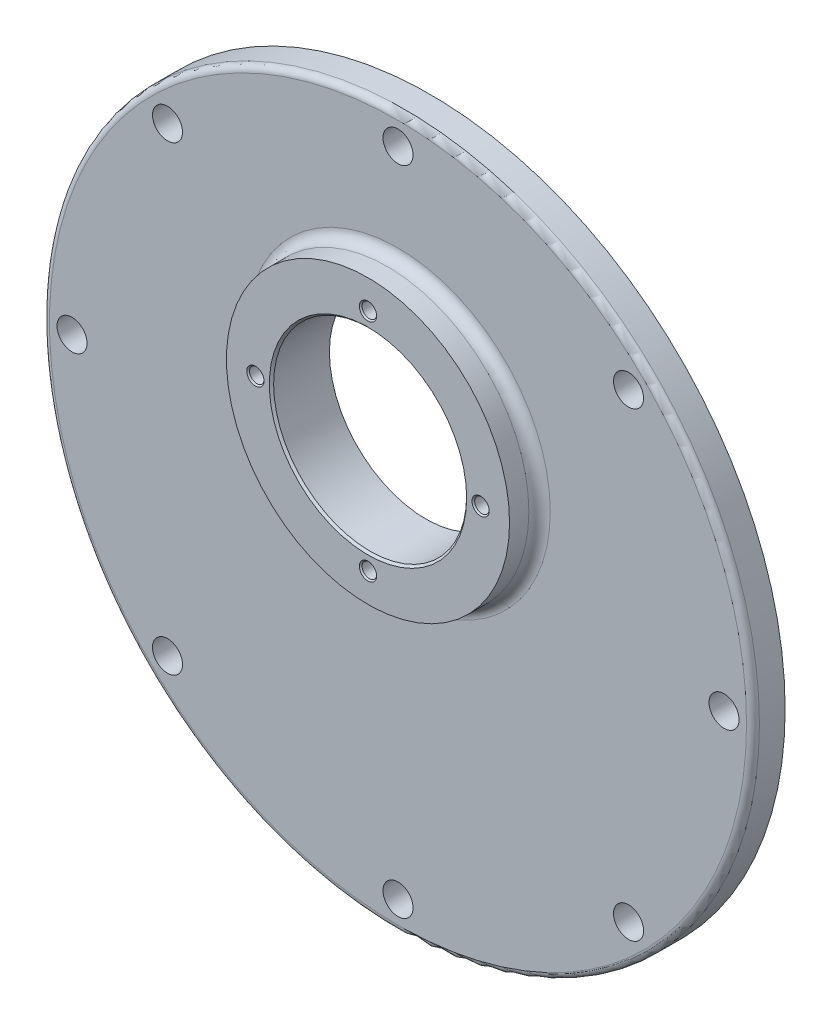
SolidWorks part; units mm, degrees
ref_plane "前视基准面" through (0, 0, 0) normal (0, 0, 1) x (1, 0, 0)
ref_plane "上视基准面" through (0, 0, 0) normal (0, 1, 0) x (1, 0, 0)
ref_plane "右视基准面" through (0, 0, 0) normal (1, 0, 0) x (0, 0, -1)
sketch "草图1" plane through (0, 0, 0) normal (0, 0, 1) x (1, 0, 0)
  circle A0 centre (0, 0) radius 140
  dimension "D1" = 280
extrude "凸台-拉伸1" add sketch "草图1" along normal blind 6
sketch "草图3" plane through (0, 0, 6) normal (0, 0, 1) x (1, 0, 0)
  circle A0 centre (0, 0) radius 165.5
  dimension "D1" = 331
extrude "凸台-拉伸2" add sketch "草图3" along normal offset from surface (15 mm away) 21 up to plane "前视基准面"
sketch "草图4" plane through (0, 0, 21) normal (0, 0, 1) x (1, 0, 0)
  line L0 (0, -11.55) -> (0, 11.55) construction
  line L1 (11.55, 0) -> (-11.55, 0) construction
  circle A0 centre (0, 40) radius 66
  dimension "D1" = 132
  dimension "D2" = 40
extrude "凸台-拉伸3" add sketch "草图4" along normal offset from surface (14 mm away) 35 up to face at (140, 0, 0)
fillet "圆角1" radius 5 1 edges at (66, 40, 21)
sketch "草图5" plane through (0, 0, 0) normal (0, 0, -1) x (-1, 0, 0)
  circle A0 centre (0, 0) radius 133
  dimension "D1" = 266
extrude "切除-拉伸1" cut sketch "草图5" against normal blind 11
sketch "草图6" plane through (0, 0, 11) normal (0, 0, -1) x (-1, 0, 0)
  circle A0 centre (0, 40) radius 55
  dimension "D1" = 110
extrude "凸台-拉伸4" add sketch "草图6" along normal blind 3
fillet "圆角2" radius 3 2 edges at (-133, 0, 11) (-55, 40, 11)
sketch "草图7" plane through (0, 0, 8) normal (0, 0, -1) x (-1, 0, 0)
  circle A0 centre (0, 40) radius 45
  dimension "D1" = 90
extrude "切除-拉伸2" cut sketch "草图7" against normal through all
chamfer "倒角1" distance 1 angle 45 1 edges at (-45, 40, 35)
sketch "草图8" plane through (0, 0, 35) normal (0, 0, 1) x (1, 0, 0)
  circle A0 centre (0, 40) radius 52.5 construction
  point P3 (52.5, 40)
  point P4 (0, 92.5)
  point P5 (-52.5, 40)
  point P6 (0, -12.5)
  dimension "D1" = 105
hole_wizard "M8 螺纹孔1" positions "草图8" profile "草图9" tap size "M8" standard "GB"
sketch "草图9" plane through (0, -12.5, 35) normal (1, 0, 0) x (0, -1, 0)
  line L0 (0, 0) -> (0, 16)
  line L1 (0, 16) -> (3.4, 13.9571)
  line L2 (3.4, 13.9571) -> (3.4, 0.625)
  line L3 (3.4, 0.625) -> (4.025, 0)
  line L5 (4.025, 0) -> (0, 0)
  line L6 (-3.4, 0.625) -> (-4.025, 0) construction
  line L10 (0, 16) -> (-3.4, 13.9571) construction
  line L11 (0, -6.35) -> (0, 107.95) construction
  dimension "螺纹孔钻头直径" = 6.8
  dimension "螺纹孔钻头深度" = 16
  dimension "近端锥形沉头孔直径" = 8.05
  dimension "近端锥形沉头孔角度" = 90
  dimension "导头角度" = 118
cosmetic thread "孔螺纹线1" parameters "D1"=14, "D2"=8
cosmetic thread "孔螺纹线2" parameters "D1"=14, "D2"=8
cosmetic thread "孔螺纹线3" parameters "D1"=14, "D2"=8
cosmetic thread "孔螺纹线4" parameters "D1"=14, "D2"=8
fillet "圆角3" radius 3 1 edges at (165.5, 0, 21)
sketch "草图10" plane through (0, 0, 21) normal (0, 0, 1) x (1, 0, 0)
  circle A0 centre (0, 0) radius 152 construction
  point P3 (152, 0)
  point P6 (107.4802, -107.4802)
  point P7 (0, -152)
  point P8 (-107.4802, -107.4802)
  point P9 (-152, 0)
  point P10 (-107.4802, 107.4802)
  point P11 (0, 152)
  point P12 (107.4802, 107.4802)
  dimension "D1" = 304
  dimension "D2" = 8
hole_wizard "孔1" positions "草图10" profile "草图11" legacy end condition through all
sketch "草图11" plane through (107.4802, 107.4802, 21) normal (1, 0, 0) x (0, -1, 0)
  line L0 (0, 0) -> (0, 21)
  line L1 (0, 21) -> (4.4, 21)
  line L2 (4.4, 21) -> (4.4, 10)
  line L3 (4.4, 10) -> (7, 10)
  line L4 (7, 10) -> (7, 0)
  line L5 (7, 0) -> (0, 0)
  line L6 (0, 110) -> (0, -10) construction
  dimension "直径" = 8.8
  dimension "深度" = 21
  dimension "柱坑直径" = 14
  dimension "柱坑深度" = 10
